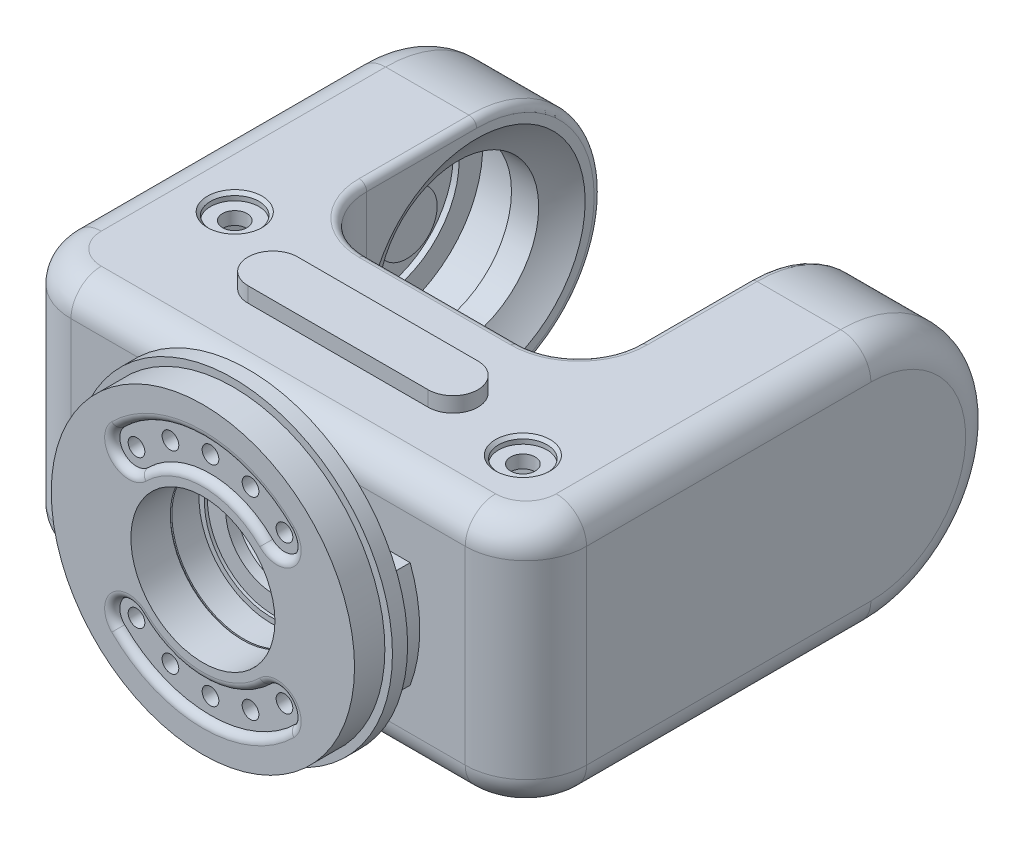
SolidWorks part; units mm, degrees
ref_plane "前视基准面" through (0, 0, 0) normal (0, 0, 1) x (1, 0, 0)
ref_plane "上视基准面" through (0, 0, 0) normal (0, 1, 0) x (1, 0, 0)
ref_plane "右视基准面" through (0, 0, 0) normal (1, 0, 0) x (0, 0, -1)
sketch "Sketch1" plane through (0, 0, 0) normal (0, 0, 1) x (1, 0, 0)
  circle A0 centre (0, 0) radius 100
  dimension "D1" = 200
extrude "Extrude1" add sketch "Sketch1" along normal mid plane 30
sketch "Sketch2" plane through (0, 0, 15) normal (0, 0, 1) x (1, 0, 0)
  line L0 (0, 0) -> (0, 100) construction
  line L1 (-48.7904, 48.7904) -> (0, 0) construction
  line L2 (0, 0) -> (100, 0) construction
  arc A0 (48.7904, 48.7904) -> (-48.7904, 48.7904) centre (0, 0) ccw construction
  arc A1 (56.5685, 56.5685) -> (-56.5685, 56.5685) centre (0, 0) ccw
  arc A2 (41.0122, 41.0122) -> (-41.0122, 41.0122) centre (0, 0) ccw
  arc A3 (41.0122, 41.0122) -> (56.5685, 56.5685) centre (48.7904, 48.7904) ccw
  arc A4 (-56.5685, 56.5685) -> (-41.0122, 41.0122) centre (-48.7904, 48.7904) ccw
  circle A5 centre (0, 0) radius 100 construction
  arc A6 (48.7904, -48.7904) -> (-48.7904, -48.7904) centre (0, 0) cw construction
  arc A7 (56.5685, -56.5685) -> (-56.5685, -56.5685) centre (0, 0) cw
  arc A8 (41.0122, -41.0122) -> (-41.0122, -41.0122) centre (0, 0) cw
  arc A9 (41.0122, -41.0122) -> (56.5685, -56.5685) centre (48.7904, -48.7904) cw
  arc A10 (-56.5685, -56.5685) -> (-41.0122, -41.0122) centre (-48.7904, -48.7904) cw
  point P4 (0, 69)
  point P18 (0, -69)
  point P23 (26.4052, 63.7477)
  point P24 (0, 69)
  point P25 (-26.4052, 63.7477)
  point P26 (26.4052, -63.7477)
  point P27 (0, -69)
  point P28 (-26.4052, -63.7477)
  dimension "D1" = 11
  dimension "D2" = 69
  dimension "D3" = 45
sketch "Sketch4" plane through (0, 0, -15) normal (0, 0, -1) x (-1, 0, 0)
  point P0 (48.7904, -48.7904)
  point P2 (26.4052, -63.7477)
  point P4 (0, -69)
  point P6 (-26.4052, -63.7477)
  point P8 (-48.7904, -48.7904)
  point P10 (48.7904, 48.7904)
  point P12 (26.4052, 63.7477)
  point P14 (0, 69)
  point P16 (-26.4052, 63.7477)
  point P18 (-48.7904, 48.7904)
hole_wizard "Ø11.0 (11) Diameter Hole3" positions "Sketch6" profile "Sketch7" hole size "Ø11.0" standard "GB" end condition through all
sketch "Sketch6" plane through (0, 0, -15) normal (0, 0, -1) x (-1, 0, 0)
  point P0 (-48.7904, 48.7904)
  point P3 (-26.4052, 63.7477)
  point P6 (0, 69)
  point P9 (26.4052, 63.7477)
  point P12 (48.7904, 48.7904)
  point P15 (48.7904, -48.7904)
  point P18 (26.4052, -63.7477)
  point P21 (0, -69)
  point P24 (-26.4052, -63.7477)
  point P27 (-48.7904, -48.7904)
sketch "Sketch7" plane through (48.7904, 48.7904, -15) normal (1, 0, 0) x (0, 1, 0)
  line L0 (0, 0) -> (0, 30)
  line L1 (0, 30) -> (5.5, 30)
  line L2 (5.5, 30) -> (5.5, 0)
  line L5 (5.5, 0) -> (0, 0)
  line L11 (0, -6.35) -> (0, 107.95) construction
  dimension "通孔孔直径" = 11
  dimension "通孔孔深度" = 30
extrude "Extrude2" cut sketch "Sketch2" against normal blind 5
sketch "Sketch8" plane through (0, 0, -15) normal (0, 0, -1) x (-1, 0, 0)
  line L0 (-64.8632, 46.8269) -> (-47.0259, 33.9495)
  line L1 (0, 0) -> (41.0122, 0) construction
  line L2 (0, 0) -> (0, 33.9495) construction
  line L3 (64.8632, 46.8269) -> (47.0259, 33.9495)
  line L4 (64.8632, -46.8269) -> (47.0259, -33.9495)
  line L5 (-64.8632, -46.8269) -> (-47.0259, -33.9495)
  circle A0 centre (-48.7904, -48.7904) radius 5.5 construction
  circle A1 centre (-26.4052, -63.7477) radius 5.5 construction
  circle A2 centre (0, -69) radius 5.5 construction
  circle A3 centre (26.4052, -63.7477) radius 5.5 construction
  arc A4 (-56.5685, 56.5685) -> (-41.0122, 41.0122) centre (-48.7904, 48.7904) ccw
  arc A5 (56.5685, 56.5685) -> (-56.5685, 56.5685) centre (0, 0) ccw
  arc A6 (41.0122, 41.0122) -> (56.5685, 56.5685) centre (48.7904, 48.7904) ccw
  arc A7 (41.0122, 41.0122) -> (-41.0122, 41.0122) centre (0, 0) ccw
  arc A8 (-56.5685, 56.5685) -> (-41.0122, 41.0122) centre (-48.7904, 48.7904) ccw construction
  arc A9 (56.5685, 56.5685) -> (-64.8632, 46.8269) centre (0, 0) ccw
  arc A10 (41.0122, 41.0122) -> (56.5685, 56.5685) centre (48.7904, 48.7904) ccw construction
  arc A11 (41.0122, 41.0122) -> (-47.0259, 33.9495) centre (0, 0) ccw
  arc A12 (-41.0122, -41.0122) -> (-56.5685, -56.5685) centre (-48.7904, -48.7904) ccw
  arc A13 (-41.0122, -41.0122) -> (41.0122, -41.0122) centre (0, 0) ccw
  arc A14 (56.5685, -56.5685) -> (41.0122, -41.0122) centre (48.7904, -48.7904) ccw
  arc A15 (-56.5685, -56.5685) -> (56.5685, -56.5685) centre (0, 0) ccw
  arc A16 (-41.0122, -41.0122) -> (-56.5685, -56.5685) centre (-48.7904, -48.7904) ccw construction
  arc A17 (-41.0122, -41.0122) -> (47.0259, -33.9495) centre (0, 0) ccw
  arc A18 (56.5685, -56.5685) -> (41.0122, -41.0122) centre (48.7904, -48.7904) ccw construction
  arc A19 (-56.5685, -56.5685) -> (64.8632, -46.8269) centre (0, 0) ccw
  circle A20 centre (48.7904, -48.7904) radius 5.5 construction
  circle A21 centre (48.7904, 48.7904) radius 5.5 construction
  circle A22 centre (26.4052, 63.7477) radius 5.5 construction
  circle A23 centre (0, 69) radius 5.5 construction
  circle A24 centre (-26.4052, 63.7477) radius 5.5 construction
  circle A25 centre (-48.7904, 48.7904) radius 5.5 construction
  circle A26 centre (-48.7904, -48.7904) radius 5.5
  circle A27 centre (-26.4052, -63.7477) radius 5.5
  circle A28 centre (0, -69) radius 5.5
  circle A29 centre (26.4052, -63.7477) radius 5.5
  circle A30 centre (48.7904, -48.7904) radius 5.5
  circle A31 centre (48.7904, 48.7904) radius 5.5
  circle A32 centre (26.4052, 63.7477) radius 5.5
  circle A33 centre (0, 69) radius 5.5
  circle A34 centre (-26.4052, 63.7477) radius 5.5
  circle A35 centre (-48.7904, 48.7904) radius 5.5
  arc A36 (-47.0259, -33.9495) -> (-41.0122, -41.0122) centre (0, 0) ccw
  arc A37 (-64.8632, -46.8269) -> (-56.5685, -56.5685) centre (0, 0) ccw
  arc A38 (47.0259, 33.9495) -> (41.0122, 41.0122) centre (0, 0) ccw
  arc A39 (64.8632, 46.8269) -> (56.5685, 56.5685) centre (0, 0) ccw
  dimension "D1" = 0
  dimension "D2" = 0
extrude "Extrude4" [suppressed] add sketch "Sketch8" along normal blind 5
fillet "Fillet1" radius 5 8 edges at (-56.5685, -41.0122, 15) (0, -80, 15) (56.5685, -41.0122, 15) (0, -58, 15) (0, 80, 15) (-56.5685, 41.0122, 15) (56.5685, 41.0122, 15) (0, 58, 15)
sketch "Sketch12" plane through (0, 0, -15) normal (0, 0, -1) x (-1, 0, 0)
  circle A0 centre (0, 0) radius 58
  dimension "D1" = 116
extrude "Extrude6" add sketch "Sketch12" along normal blind 23
sketch "Sketch15" plane through (0, 0, 0) normal (0, 1, 0) x (1, 0, 0)
  line L0 (0, -15) -> (0, 38) construction
  line L17 (-100, -15) -> (100, -15) construction
  line L18 (58, 38) -> (-58, 38) construction
  line L19 (0, 38) -> (32, 38)
  line L20 (32, 38) -> (32, 32)
  line L21 (32, 32) -> (44, 32)
  line L22 (44, 32) -> (44, 30)
  line L23 (44, 30) -> (47.5, 30)
  line L24 (47.5, 30) -> (47.5, 12)
  line L25 (47.5, 12) -> (48.5, 12)
  line L26 (48.5, 12) -> (48.5, 11)
  line L27 (48.5, 11) -> (47.5, 11)
  line L28 (47.5, 11) -> (47.5, -15)
  line L29 (47.5, -15) -> (0, -15)
  line L30 (0, 38) -> (0, -15)
  dimension "D1" = 95
  dimension "D2" = 97
  dimension "D3" = 64
  dimension "D4" = 88
  dimension "D5" = 2
  dimension "D6" = 1
  dimension "D7" = 18
  dimension "D8" = 6
revolve "Cut-Revolve1" cut sketch "Sketch15" angle 360 about L0
sketch "Sketch16" plane through (0, 0, -38) normal (0, 0, -1) x (-1, 0, 0)
  line L0 (0, 0) -> (100, 0) construction
  line L1 (-93.675, 35) -> (-46.2493, 35)
  line L2 (-93.675, -35) -> (-46.2493, -35)
  line L3 (46.2493, 35) -> (93.675, 35)
  line L4 (46.2493, -35) -> (93.675, -35)
  circle A0 centre (0, 0) radius 100 construction
  arc A1 (-93.675, 35) -> (-93.675, -35) centre (0, 0) ccw
  arc A2 (93.675, 35) -> (93.675, -35) centre (0, 0) cw
  arc A3 (-46.2493, 35) -> (-46.2493, -35) centre (0, 0) ccw
  circle A4 centre (0, 0) radius 58 construction
  arc A5 (46.2493, 35) -> (46.2493, -35) centre (0, 0) cw
  circle A6 centre (0, 0) radius 58 construction
  dimension "D3" = 100
  dimension "D4" = 100
  dimension "D5" = 58
  dimension "D6" = 58
  dimension "D1" = 35
  dimension "D2" = 35
extrude "Extrude7" add sketch "Sketch16" against normal up to next
sketch "Sketch20" plane through (0, 0, 0) normal (0, 1, 0) x (1, 0, 0)
  line L2 (-50, 143) -> (50, 143)
  line L3 (0, -15) -> (0, 38) construction
  line L4 (-100, -15) -> (100, -15) construction
  line L5 (-170, 68) -> (-170, 338)
  line L6 (-170, 338) -> (-90, 338)
  line L7 (-90, 338) -> (-90, 183)
  line L8 (90, 338) -> (90, 183)
  line L9 (170, 338) -> (90, 338)
  line L10 (170, 68) -> (170, 338)
  line L11 (-130, 28) -> (130, 28)
  line L12 (46.2493, 38) -> (-46.2493, 38) construction
  arc A0 (-50, 143) -> (-90, 183) centre (-50, 183) cw
  arc A1 (-130, 28) -> (-170, 68) centre (-130, 68) cw
  arc A2 (130, 28) -> (170, 68) centre (130, 68) ccw
  arc A3 (50, 143) -> (90, 183) centre (50, 183) ccw
  dimension "D2" = 40
  dimension "D1" = 10
  dimension "D3" = 340
  dimension "D4" = 180
extrude "Extrude12" add sketch "Sketch20" along normal mid plane 165
fillet "Fillet2" 2 edges at (130, 82.5, -338) (130, -82.5, -338) type full round first side face at (0, 82.5, -180.2386) second side face at (0, -82.5, -180.2386) middle face at (130, 0, -338)
fillet "Fillet3" 2 edges at (-130, -82.5, -338) (-130, 82.5, -338) type full round first side face at (0, -82.5, -166.4886) second side face at (0, 82.5, -166.4886) middle face at (-130, 0, -338)
sketch "Sketch21" plane through (0, 0, 0) normal (0, 1, 0) x (1, 0, 0)
  line L0 (-90, 255.5) -> (90, 255.5) construction
  line L1 (0, 370.5) -> (0, 153)
  line L2 (0, 153) -> (52.1416, 153)
  line L3 (50, 143) -> (-50, 143) construction
  arc A0 (52.1416, 153) -> (0, 370.5) centre (0, 255.5) ccw
  dimension "D1" = 230
  dimension "D2" = 10
revolve "Cut-Revolve2" cut sketch "Sketch21" angle 360 about L1
sketch "Sketch23" plane through (0, 0, 0) normal (0, 1, 0) x (1, 0, 0)
  line L0 (-155, 255.5) -> (-120, 255.5)
  line L1 (-120, 255.5) -> (-120, 168)
  line L2 (-80, 128) -> (80, 128)
  line L3 (120, 168) -> (120, 255.5)
  line L4 (120, 255.5) -> (155, 255.5)
  line L5 (155, 255.5) -> (155, 86)
  line L6 (115, 46) -> (-115, 46)
  line L7 (-155, 86) -> (-155, 255.5)
  line L9 (50, 143) -> (-50, 143) construction
  line L10 (170, 68) -> (170, 255.5) construction
  line L11 (-90, 255.5) -> (-170, 255.5) construction
  line L12 (-170, 255.5) -> (-170, 68) construction
  line L13 (93.675, 28) -> (46.2493, 28) construction
  arc A0 (-120, 168) -> (-80, 128) centre (-80, 168) ccw
  arc A1 (80, 128) -> (120, 168) centre (80, 168) ccw
  arc A2 (155, 86) -> (115, 46) centre (115, 86) cw
  arc A3 (-115, 46) -> (-155, 86) centre (-115, 86) cw
  arc A4 (90, 183.9109) -> (90, 327.0891) centre (0, 255.5) ccw construction
  arc A5 (50, 143) -> (90, 183) centre (50, 183) ccw construction
  arc A6 (-90, 327.0891) -> (-90, 183.9109) centre (0, 255.5) ccw construction
  arc A7 (-90, 183) -> (-50, 143) centre (-50, 183) ccw construction
  dimension "D6" = 40
  dimension "D1" = 18
  dimension "D2" = 15
  dimension "D3" = 15
  dimension "D4" = 15
  dimension "D5" = 5
  dimension "D7" = 5
extrude "Extrude13" cut sketch "Sketch23" against normal mid plane 138
fillet "Fillet4" radius 20 12 edges at (-158.2843, 82.5, -39.7157) (-170, 82.5, -161.75) (-170, 0, -338) (-170, -82.5, -161.75) (-158.2843, -82.5, -39.7157) (158.2843, -82.5, -39.7157) (170, -82.5, -161.75) (170, 0, -338) (170, 82.5, -161.75) (158.2843, 82.5, -39.7157) (0, -82.5, -28) (0, 82.5, -28)
sketch "Sketch24" plane through (0, 0, 0) normal (1, 0, 0) x (0, 0, -1)
  circle A0 centre (255.5, 0) radius 53
  dimension "D1" = 106
extrude "Extrude14" cut sketch "Sketch24" against normal mid plane 310
sketch "Sketch27" plane through (-155, 0, 0) normal (1, 0, 0) x (0, 0, -1)
  line L0 (255.5, 69) -> (86, 69) construction
  circle A0 centre (255.5, 0) radius 69
extrude "Extrude16" cut sketch "Sketch27" along normal up to surface (35 mm away) up to face at (-120, 0, -217.5)
sketch "Sketch28" plane through (155, 0, 0) normal (-1, 0, 0) x (0, 0, 1)
  line L0 (-86, -69) -> (-255.5, -69) construction
  circle A0 centre (-255.5, 0) radius 69
extrude "Extrude17" cut sketch "Sketch28" along normal up to surface (35 mm away) up to face at (120, 0, -217.5)
sketch "Sketch29" plane through (0, 0, 0) normal (0, 1, 0) x (1, 0, 0)
  line L0 (0, -15) -> (0, 28) construction
  line L1 (-100, -15) -> (100, -15) construction
  line L2 (-46.2493, 28) -> (46.2493, 28) construction
  line L7 (0, 28) -> (47.5, 28)
  line L8 (47.5, 28) -> (47.5, 30)
  line L9 (47.5, 30) -> (44, 30)
  line L11 (44, 30) -> (44, 32)
  line L12 (44, 32) -> (32, 32)
  line L14 (32, 32) -> (32, 39)
  line L15 (32, 39) -> (53.5, 39)
  line L16 (53.5, 39) -> (53.5, 127)
  line L18 (53.5, 127) -> (34.5, 127)
  line L19 (34.5, 127) -> (34.5, 143)
  line L22 (50, 143) -> (-50, 143) construction
  line L24 (0, 143) -> (0, 28)
  line L25 (0, 143) -> (34.5, 143)
  dimension "D1" = 95
  dimension "D2" = 2
  dimension "D3" = 2
  dimension "D4" = 88
  dimension "D5" = 64
  dimension "D6" = 7
  dimension "D7" = 107
  dimension "D8" = 69
  dimension "D9" = 16
revolve "Cut-Revolve3" cut sketch "Sketch29" angle 360 about L0
sketch "Sketch30" plane through (-155, 0, 0) normal (1, 0, 0) x (0, 0, -1)
  circle A0 centre (255.5, 0) radius 53.5
  dimension "D1" = 107
extrude "Extrude18" cut sketch "Sketch30" against normal blind 4
mirror "Mirror1" about plane through (0, 0, 0) normal (1, 0, 0) of "Extrude18"
sketch "Sketch33" plane through (0, 0, 0) normal (0, 1, 0) x (1, 0, 0)
  line L0 (170, 255.5) -> (200.3092, 255.5) construction
  line L1 (159, 255.5) -> (159, 278)
  line L2 (90, 255.5) -> (150, 255.5) construction
  line L3 (159, 278) -> (151, 278)
  line L4 (151, 278) -> (151, 275.5)
  line L5 (151, 275.5) -> (136, 275.5)
  line L6 (136, 275.5) -> (136, 255.5)
  line L7 (136, 255.5) -> (159, 255.5)
  line L8 (159, 309) -> (159, 202) construction
  dimension "D1" = 45
  dimension "D2" = 40
  dimension "D3" = 8
  dimension "D4" = 15
revolve "Revolve1" add sketch "Sketch33" angle 360 about L0
mirror "Mirror2" about plane through (0, 0, 0) normal (1, 0, 0) of "Revolve1"
fillet "Fillet5" radius 8 2 edges at (-159, 0, -233) (159, 0, -233)
sketch "Sketch34" plane through (0, 69, 0) normal (0, -1, 0) x (1, 0, 0)
  line L0 (-120, -168) -> (-120, -255.5) construction
  line L1 (80, -128) -> (-80, -128) construction
  line L6 (120, -255.5) -> (120, -168) construction
  circle A0 centre (-117, -123) radius 18 construction
  circle A1 centre (117, -79) radius 18 construction
  circle A2 centre (-117, -123) radius 24 construction
  circle A3 centre (117, -79) radius 24 construction
  circle A4 centre (-117, -123) radius 26
  dimension "D3" = 36
  dimension "D4" = 15
  dimension "D5" = 67
  dimension "D6" = 36
  dimension "D7" = 48
  dimension "D8" = 48
  dimension "D9" = 52
  dimension "D1" = 15
  dimension "D2" = 23
extrude "Extrude19" cut sketch "Sketch34" along normal up to surface (138 mm away) up to face at (0, -69, -153.7386)
sketch "Sketch35" plane through (0, -82.5, 0) normal (0, -1, 0) x (1, 0, 0)
  circle A0 centre (-117, -123) radius 16
  circle A1 centre (117, -79) radius 16
  dimension "D1" = 32
  dimension "D2" = 32
extrude "Extrude21" cut sketch "Sketch35" against normal blind 5
mirror "Mirror5" about plane through (0, 0, 0) normal (0, 1, 0) of "Extrude21"
chamfer "Chamfer2" distance 2 angle 45 4 edges at (117, 82.5, -95) (-117, 82.5, -139) (117, -82.5, -95) (-117, -82.5, -139)
sketch "Sketch36" plane through (0, 0, 0) normal (0, 1, 0) x (1, 0, 0)
  circle A0 centre (-117, 123) radius 8.1
  circle A1 centre (117, 79) radius 8.1
  dimension "D1" = 16.2
extrude "Extrude22" cut sketch "Sketch36" along normal through all both and the other way through all
fillet "Fillet6" radius 5 12 edges at (-78.2843, 82.5, -154.7157) (0, 82.5, -143) (78.2843, 82.5, -154.7157) (90, 82.5, -219.25) (90, 0, -338) (90, -82.5, -219.25) (78.2843, -82.5, -154.7157) (0, -82.5, -143) (-78.2843, -82.5, -154.7157) (-90, -82.5, -219.25) (-90, 0, -338) (-90, 82.5, -219.25)
sketch "Sketch37" plane through (0, 0, -15) normal (0, 0, -1) x (-1, 0, 0)
  circle A0 centre (0, 0) radius 100
  circle A1 centre (0, 0) radius 105
  dimension "D1" = 200
  dimension "D2" = 210
extrude "Extrude23" add sketch "Sketch37" against normal blind 10
ref_axis "Axis1" through (-95, 0, -255.5) along (-1, 0, 0)
sketch "Sketch39" plane through (0, 82.5, 0) normal (0, 1, 0) x (1, 0, 0)
  line L0 (-60.4724, 91.6073) -> (58.3452, 91.6073) construction
  line L1 (-60.4724, 108.0169) -> (58.3452, 108.0169)
  line L2 (-60.4724, 75.1977) -> (58.3452, 75.1977)
  arc A0 (-60.4724, 108.0169) -> (-60.4724, 75.1977) centre (-60.4724, 91.6073) ccw
  arc A1 (58.3452, 75.1977) -> (58.3452, 108.0169) centre (58.3452, 91.6073) ccw
  point P2 (-1.0636, 91.6073)
extrude "Boss-Extrude1" add sketch "Sketch39" along normal blind 10
